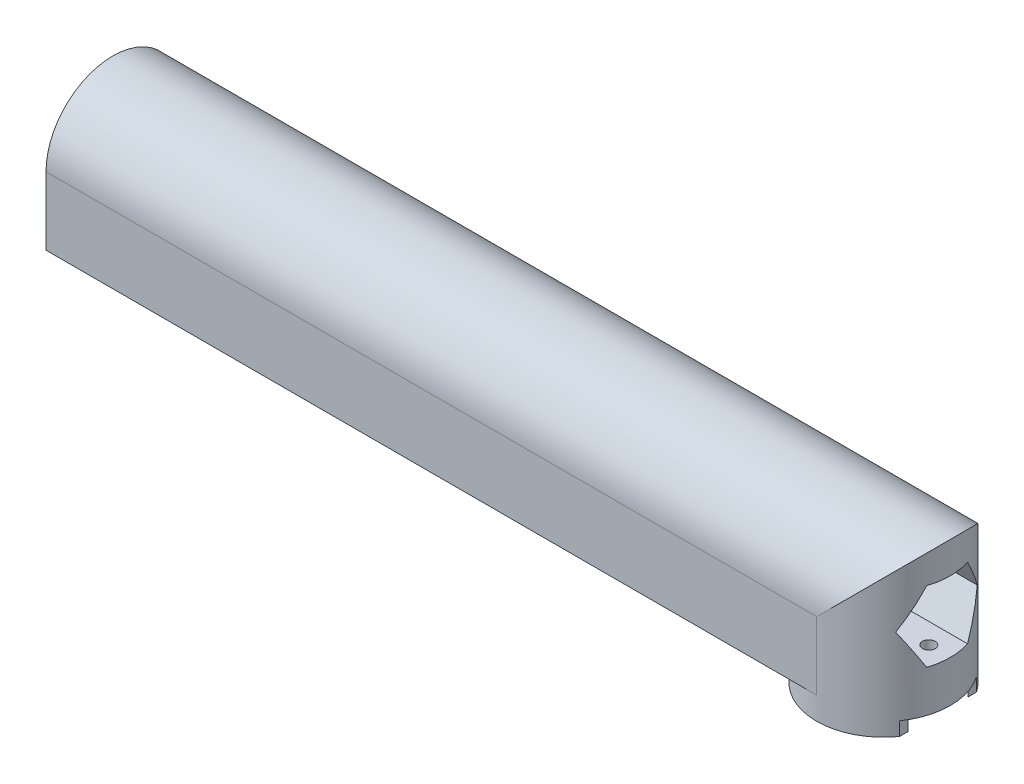
SolidWorks part; units mm, degrees
ref_plane "Plan de face" through (0, 0, 0) normal (0, 0, 1) x (1, 0, 0)
ref_plane "Plan de dessus" through (0, 0, 0) normal (0, 1, 0) x (1, 0, 0)
ref_plane "Plan de droite" through (0, 0, 0) normal (1, 0, 0) x (0, 0, -1)
sketch "Esquisse1" plane through (0, 0, 0) normal (0, 1, 0) x (1, 0, 0)
  circle A0 centre (0, 0) radius 14.75
  dimension "D1" = 29.5
extrude "Boss.-Extru.1" add sketch "Esquisse1" along normal blind 5
sketch "Esquisse2" plane through (0, 0, 0) normal (0, -1, 0) x (1, 0, 0)
  circle A0 centre (0, 0) radius 13.75
  dimension "D1" = 27.5
extrude "Enlèv. mat.-Extru.1" cut sketch "Esquisse2" against normal blind 3
sketch "Esquisse3" plane through (0, 0, 0) normal (0, -1, 0) x (1, 0, 0)
  line L0 (13.75, 0) -> (-13.75, 0) construction
  line L1 (-12.0546, 8.5) -> (-12.0546, -8.5)
  line L2 (12.0546, 8.5) -> (12.0546, -8.5)
  circle A0 centre (0, 0) radius 13.75 construction
  circle A1 centre (0, 0) radius 13.75 construction
  circle A2 centre (0, 0) radius 14.75 construction
  arc A3 (-12.0546, 8.5) -> (-12.0546, -8.5) centre (0, 0) ccw
  arc A4 (12.0546, 8.5) -> (12.0546, -8.5) centre (0, 0) cw
  dimension "D1" = 17
  dimension "D2" = 17
extrude "Enlèv. mat.-Extru.2" cut sketch "Esquisse3" against normal blind 3
sketch "Esquisse5" plane through (0, 5, 0) normal (0, 1, 0) x (1, 0, 0)
  circle A0 centre (0, 0) radius 14.75
  circle A1 centre (0, 0) radius 14.75 construction
extrude "Boss.-Extru.2" add sketch "Esquisse5" along normal blind 30
sketch "Esquisse7" plane through (0, 35, 0) normal (0, 1, 0) x (1, 0, 0)
  line L0 (0, -14.75) -> (0, 14.75)
  arc A0 (0, -14.75) -> (0, 14.75) centre (0, 0) cw
  circle A1 centre (0, 0) radius 14.75 construction
extrude "Enlèv. mat.-Extru.6" cut sketch "Esquisse7" against normal blind 30
sketch "Esquisse8" plane through (0, 0, 0) normal (-1, 0, 0) x (0, 0, 1)
  line L0 (-14.75, 5) -> (-14.75, 35) construction
  line L1 (14.75, 5) -> (14.75, 35) construction
  line L5 (-14.75, 20) -> (-14.75, 35)
  line L6 (-14.75, 35) -> (14.75, 35)
  line L7 (14.75, 35) -> (14.75, 20)
  arc A1 (-14.75, 20) -> (14.75, 20) centre (0, 20) cw
extrude "Enlèv. mat.-Extru.7" cut sketch "Esquisse8" against normal blind 15 contours L5 L6 L7 A1
sketch "Esquisse10" plane through (0, 0, 0) normal (-1, 0, 0) x (0, 0, 1)
  line L0 (-14.75, 20) -> (-14.75, 5)
  line L1 (-14.75, 5) -> (14.75, 5)
  line L2 (14.75, 5) -> (14.75, 20)
  arc A0 (-14.75, 20) -> (14.75, 20) centre (0, 20) cw
extrude "Boss.-Extru.3" add sketch "Esquisse10" along normal blind 170
sketch "Esquisse11" plane through (-170, 0, 0) normal (-1, 0, 0) x (0, 0, 1)
  line L0 (-14.75, 20) -> (14.75, 20) construction
  line L1 (-9, 20) -> (9, 20)
  line L2 (-9, 20) -> (-4.5, 27.7942)
  line L3 (-4.5, 27.7942) -> (4.5, 27.7942)
  line L4 (4.5, 27.7942) -> (9, 20)
  line L5 (9, 20) -> (4.5, 12.2058)
  line L6 (4.5, 12.2058) -> (-4.5, 12.2058)
  line L7 (-4.5, 12.2058) -> (-9, 20)
  point P7 (0, 20)
  point P8 (0, 20)
  dimension "D1" = 18
  dimension "D2" = 18
extrude "Enlèv. mat.-Extru.8" cut sketch "Esquisse11" against normal through all contours L4 L3 L2 L1 | L7 L6 L5 L1 region at (-170, 23.4641, 0) region at (-170, 16.5359, 0)
sketch "Esquisse6" plane through (0, 3, 0) normal (0, -1, 0) x (1, 0, 0)
  circle A0 centre (0, 10) radius 1.4
  circle A1 centre (7.0711, 7.0711) radius 1.4
  circle A2 centre (10, 0) radius 1.4
  circle A3 centre (7.0711, -7.0711) radius 1.4
  circle A4 centre (0, -10) radius 1.4
  circle A5 centre (-7.0711, -7.0711) radius 1.4
  circle A6 centre (-10, 0) radius 1.4
  circle A7 centre (-7.0711, 7.0711) radius 1.4
  point P20 (0, 0)
  dimension "D1" = 2.8
  dimension "D2" = 10
  dimension "D3" = 8
extrude "Enlèv. mat.-Extru.5" cut sketch "Esquisse6" against normal blind 10
